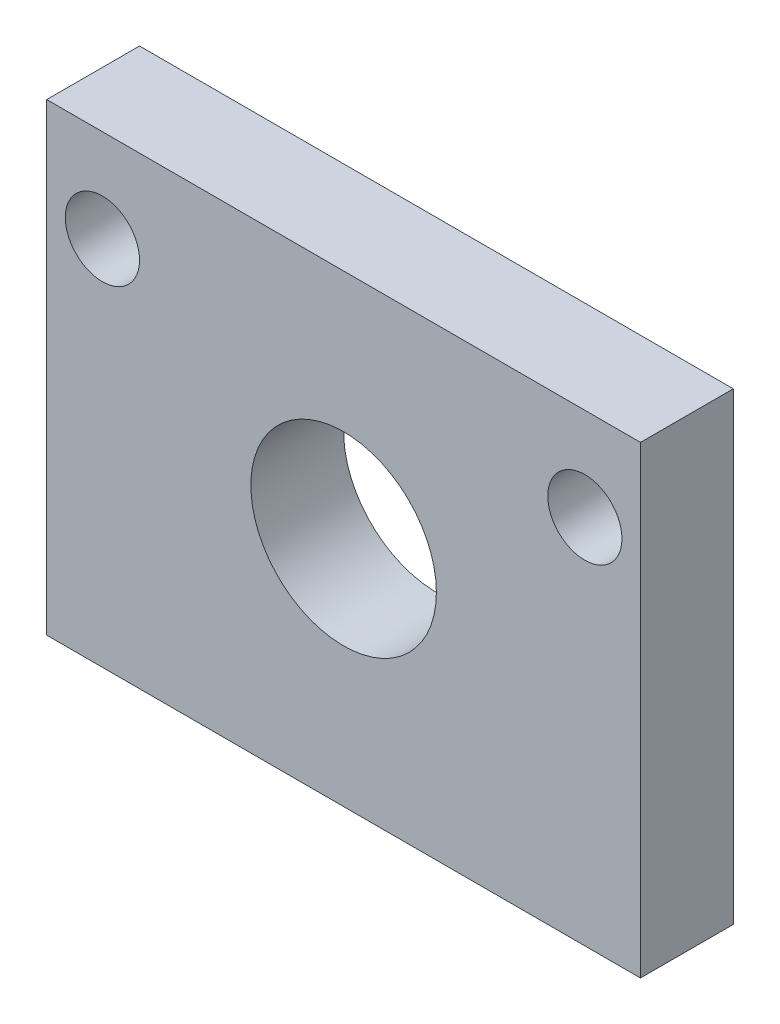
SolidWorks part; units mm, degrees
ref_plane "Alzado" through (0, 0, 0) normal (0, 0, 1) x (1, 0, 0)
ref_plane "Planta" through (0, 0, 0) normal (0, 1, 0) x (1, 0, 0)
ref_plane "Vista lateral" through (0, 0, 0) normal (1, 0, 0) x (0, 0, -1)
sketch "Croquis1" plane through (0, 0, 0) normal (0, 0, 1) x (1, 0, 0)
  line L1 (-16, -12.5) -> (16, -12.5)
  line L2 (-16, -12.5) -> (-16, 12.5)
  line L3 (-16, 12.5) -> (16, 12.5)
  line L4 (16, -12.5) -> (16, 12.5)
  line L5 (-16, -12.5) -> (16, 12.5) construction
  line L6 (-16, 12.5) -> (16, -12.5) construction
  circle A0 centre (0, 0) radius 5
  circle A1 centre (-13, 7.5) radius 2
  circle A2 centre (13, 7.5) radius 2
  point P0 (0, 0)
  dimension "D3" = 3
  dimension "D5" = 20
  dimension "D1" = 32
  dimension "D2" = 25
  dimension "D4" = 20
  dimension "D6" = 3
extrude "Saliente-Extruir1" add sketch "Croquis1" along normal blind 5
